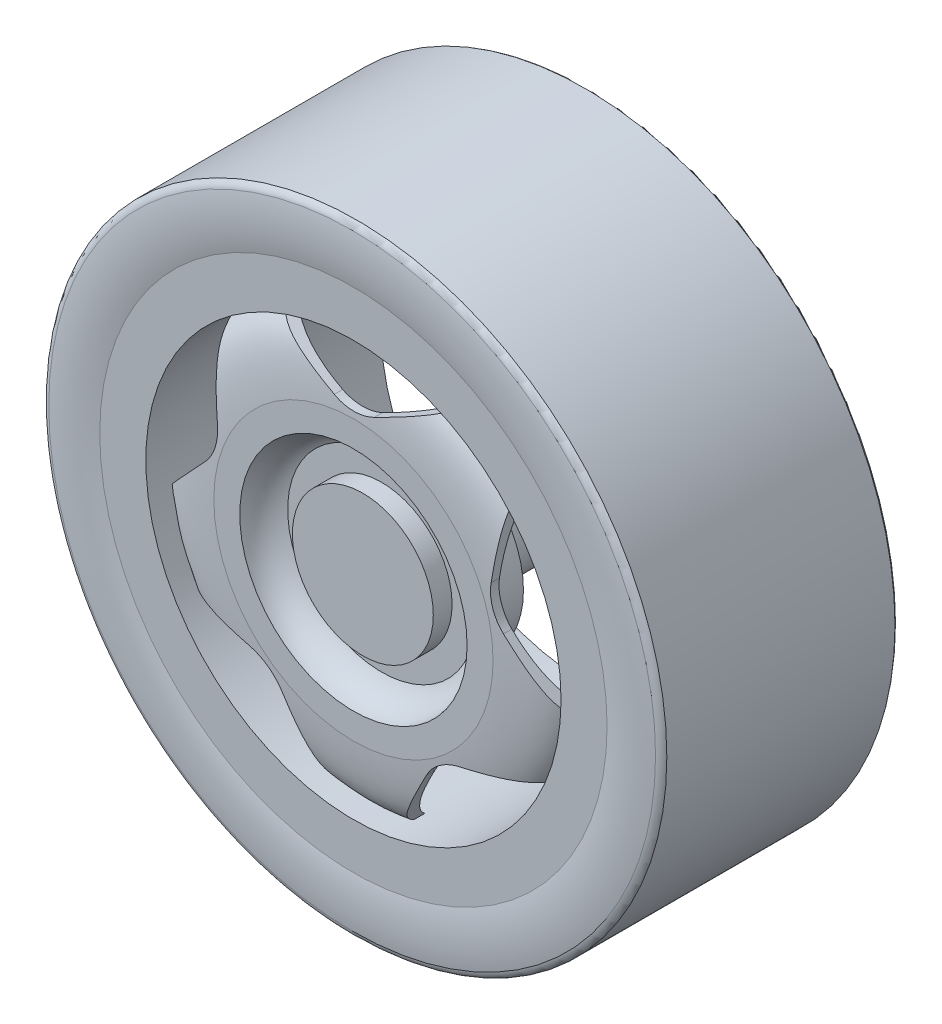
SolidWorks part; units mm, degrees
ref_plane "Front Plane" through (0, 0, 0) normal (0, 0, 1) x (1, 0, 0)
ref_plane "Top Plane" through (0, 0, 0) normal (0, 1, 0) x (1, 0, 0)
ref_plane "Right Plane" through (0, 0, 0) normal (1, 0, 0) x (0, 0, -1)
sketch "Sketch1" plane through (0, 0, 0) normal (1, 0, 0) x (0, 0, -1)
  line L0 (-0.0107, 12.1) -> (-0.0107, 14.8643)
  line L1 (-0.0107, 25.1) -> (24.9893, 25.1)
  line L2 (-0.0107, 22.1) -> (2.9893, 22.1)
  line L3 (2.9893, 10) -> (2.9893, 7.5)
  line L4 (2.9893, 7.5) -> (0.9893, 7.5)
  line L5 (0.9893, 7.5) -> (0.9893, 0)
  line L6 (-13.2759, 0) -> (14.215, 0) construction
  line L7 (-0.0107, 22.1) -> (-0.0107, 25.1)
  line L8 (24.9893, 25.1) -> (24.9893, 22.1)
  line L9 (24.9893, 22.1) -> (4.0868, 22.1)
  line L10 (0.9893, 14.8643) -> (0.9893, 12.992)
  line L11 (4.0868, 10) -> (8.0868, 10)
  line L12 (8.0868, 10) -> (8.0868, 0)
  line L13 (8.0868, 0) -> (0.9893, 0)
  arc A0 (-0.0107, 12.1) -> (2.9893, 10) centre (-0.3983, 8.3534) cw
  arc A1 (4.0868, 22.1) -> (0.9893, 14.8643) centre (9.2266, 15.6189) ccw
  arc A2 (0.9893, 12.992) -> (4.0868, 10) centre (-0.1123, 8.7522) cw
  spline S0 degree 3 poles (2.9893, 22.1) (1.2339, 21.0874) (0.2751, 20.019) (-0.0107, 14.8643) knots 0 0 0 0 1 1 1 1
  point P6 (3, 12)
  dimension "D5" = 2.2559
  dimension "D2" = 25
  dimension "D3" = 3
  dimension "D4" = 3
  dimension "D6" = 2
  dimension "D7" = 2.5
  dimension "D8" = 2
  dimension "D9" = 13
  dimension "D10" = 1
  dimension "D11" = 1
  dimension "D12" = 4
revolve "Revolve1" add sketch "Sketch1" angle 360 about L6
sketch "Sketch2" plane through (0, 0, 0.0107) normal (0, 0, 1) x (1, 0, 0)
  line L0 (0, 22.1) -> (0, 0) construction
  line L1 (-10, 19.7081) -> (-2.1298, 16.0027)
  line L2 (2.1298, 16.0027) -> (10, 19.7081)
  line L3 (15.6534, 15.6007) -> (14.5614, 6.9707)
  line L4 (15.8777, 2.9195) -> (21.8337, -3.4204)
  line L5 (19.6743, -10.0664) -> (11.1292, -11.6946)
  line L6 (7.6831, -14.1984) -> (3.494, -21.8221)
  line L7 (-3.494, -21.8221) -> (-7.6831, -14.1984)
  line L8 (-11.1292, -11.6946) -> (-19.6743, -10.0664)
  line L9 (-21.8337, -3.4204) -> (-15.8777, 2.9195)
  line L10 (-14.5614, 6.9707) -> (-15.6534, 15.6007)
  circle A0 centre (0, 0) radius 22.1 construction
  circle A1 centre (0, 0) radius 22.1 construction
  arc A2 (-2.1298, 16.0027) -> (2.1298, 16.0027) centre (0, 20.5264) ccw
  arc A3 (10, 19.7081) -> (-10, 19.7081) centre (0, 0) ccw
  arc A4 (14.5614, 6.9707) -> (15.8777, 2.9195) centre (19.5218, 6.343) ccw
  arc A5 (21.8337, -3.4204) -> (15.6534, 15.6007) centre (0, 0) ccw
  arc A6 (11.1292, -11.6946) -> (7.6831, -14.1984) centre (12.0651, -16.6062) ccw
  arc A7 (3.494, -21.8221) -> (19.6743, -10.0664) centre (0, 0) ccw
  arc A8 (-7.6831, -14.1984) -> (-11.1292, -11.6946) centre (-12.0651, -16.6062) ccw
  arc A9 (-19.6743, -10.0664) -> (-3.494, -21.8221) centre (0, 0) ccw
  arc A10 (-15.8777, 2.9195) -> (-14.5614, 6.9707) centre (-19.5218, 6.343) ccw
  arc A11 (-15.6534, 15.6007) -> (-21.8337, -3.4204) centre (0, 0) ccw
  point P12 (0, 15)
  point P35 (0, 0)
  dimension "D3" = 5
  dimension "D1" = 10
  dimension "D2" = 15
  dimension "D4" = 5
extrude "Cut-Extrude1" cut sketch "Sketch2" against normal blind 10
sketch "Sketch3" plane through (0, 0, -8.0868) normal (0, 0, -1) x (-1, 0, 0)
  circle A0 centre (0, 0) radius 6
  dimension "D1" = 12
extrude "Boss-Extrude1" add sketch "Sketch3" along normal blind 25
sketch "Sketch4" plane through (0, 0, -33.0868) normal (0, 0, -1) x (-1, 0, 0)
  line L0 (-2.5475, 2.4) -> (2.5475, 2.4)
  line L1 (-3.5, 0) -> (3.5, 0) construction
  line L2 (-2.5475, -2.4) -> (2.5475, -2.4)
  arc A0 (-2.5475, 2.4) -> (-2.5475, -2.4) centre (0, 0) ccw
  arc A1 (2.5475, -2.4) -> (2.5475, 2.4) centre (0, 0) ccw
  dimension "D1" = 7
  dimension "D2" = 2.4
extrude "Cut-Extrude2" cut sketch "Sketch4" against normal blind 12
sketch "Sketch5" plane through (0, 0, 0) normal (1, 0, 0) x (0, 0, -1)
  line L1 (-0.0107, 25.1) -> (-0.0107, -25.1) construction
  line L2 (24.9893, -25.1) -> (24.9893, 25.1) construction
  line L3 (12.4893, 34) -> (12.4893, 27) construction
  line L4 (0, 0) -> (33.0868, 0) construction
  line L5 (33.0868, -2.4) -> (33.0868, 2.4) construction
  line L6 (-0.0107, 27) -> (-0.0107, 24.9185)
  line L7 (-0.0107, 24.9185) -> (24.9893, 25.1)
  line L8 (24.9893, 25.1) -> (24.9893, 27)
  arc A0 (12.4893, 34) -> (0.6779, 33.1166) centre (11.5988, -33.4941) ccw
  arc A1 (-0.1468, 32.2936) -> (-0.0107, 27) centre (13.6641, 30) ccw
  arc A2 (-0.1468, 32.2936) -> (0.6779, 33.1166) centre (0.8397, 32.1297) cw
  arc A3 (25.1253, 32.2936) -> (24.9893, 27) centre (11.3145, 30) cw
  arc A4 (25.1253, 32.2936) -> (24.3006, 33.1166) centre (24.1389, 32.1297) ccw
  arc A5 (12.4893, 34) -> (24.3006, 33.1166) centre (13.3798, -33.4941) cw
  point P6 (12.4893, 34)
  point P7 (-0.0107, 33)
  point P8 (12.4893, 31.1)
  point P21 (-0.0107, 33)
  dimension "D3" = 67.5
  dimension "D4" = 14
  dimension "D5" = 1
  dimension "D2" = 6
  dimension "D6" = 34
revolve "Revolve2" add sketch "Sketch5" angle 360 about L4
sketch "Croquis1" plane through (0, 0, 0.0107) normal (0, 0, 1) x (1, 0, 0)
  circle A0 centre (0, 0) radius 33
  circle A1 centre (0, 0) radius 45.5599
  dimension "D1" = 66
extrude "Cortar-Extruir1" cut sketch "Croquis1" against normal blind 40
